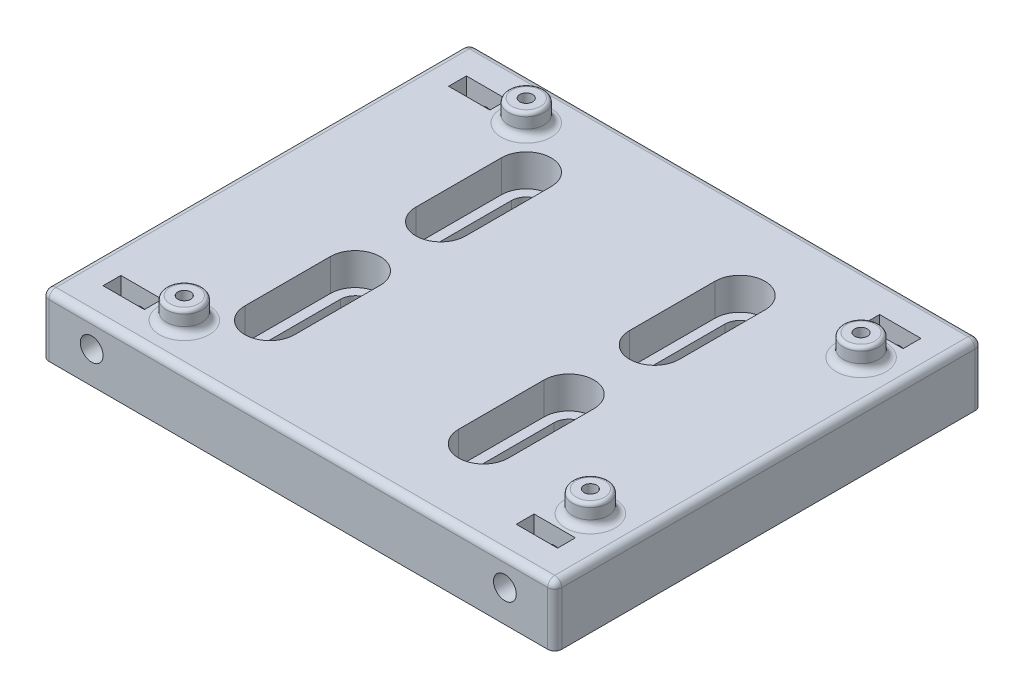
SolidWorks part; units mm, degrees
ref_plane "Front Plane" through (0, 0, 0) normal (0, 0, 1) x (1, 0, 0)
ref_plane "Top Plane" through (0, 0, 0) normal (0, 1, 0) x (1, 0, 0)
ref_plane "Right Plane" through (0, 0, 0) normal (1, 0, 0) x (0, 0, -1)
sketch "Sketch1" plane through (0, 0, 0) normal (0, 1, 0) x (1, 0, 0)
  line L0 (35, 0) -> (35, -56)
  line L1 (0, 0) -> (70, 0)
  line L2 (0, 0) -> (0, -56)
  line L3 (0, -56) -> (70, -56)
  line L4 (70, 0) -> (70, -56)
  line L5 (0, -28) -> (70, -28)
  line L6 (17.9, -10) -> (17.9, -22)
  line L7 (22.1, -22) -> (22.1, -10)
  line L8 (47.9, -22) -> (47.9, -10)
  line L9 (52.1, -10) -> (52.1, -22)
  line L10 (22.1, -34) -> (22.1, -46)
  line L11 (17.9, -46) -> (17.9, -34)
  line L12 (52.1, -46) -> (52.1, -34)
  line L13 (47.9, -34) -> (47.9, -46)
  circle A0 centre (20, -10) radius 2.1
  circle A1 centre (20, -22) radius 2.1
  circle A2 centre (50, -22) radius 2.1
  circle A3 centre (50, -10) radius 2.1
  circle A4 centre (20, -34) radius 2.1
  circle A5 centre (20, -46) radius 2.1
  circle A6 centre (50, -34) radius 2.1
  circle A7 centre (50, -46) radius 2.1
  dimension "D3" = 10
  dimension "D5" = 6
  dimension "D1" = 70
  dimension "D2" = 56
  dimension "D4" = 20
  dimension "D6" = 20
extrude "Boss-Extrude1" add sketch "Sketch1" along normal blind 4 contours L2 L5 L0 L1 A1 L6 A0 L7 | L0 L5 L4 L1 L8 A3 L9 A2 | L5 L0 L3 L4 A7 L13 A6 L12 | L5 L2 L3 L0 L10 A5 L11 A4 region at (52.6754, 0, 13.8597) region at (17.3246, 0, 13.8597) region at (52.6754, 0, 42.1403) region at (17.3246, 0, 42.1403)
sketch "Sketch2" plane through (0, 4, 0) normal (0, 1, 0) x (1, 0, 0)
  line L18 (23.5, -22) -> (23.5, -10)
  line L19 (16.5, -10) -> (16.5, -22)
  line L20 (23.5, -22) -> (23.5, -10)
  line L21 (16.5, -10) -> (16.5, -22)
  line L35 (46.5, -10) -> (46.5, -22)
  line L36 (53.5, -22) -> (53.5, -10)
  line L37 (46.5, -10) -> (46.5, -22)
  line L38 (53.5, -22) -> (53.5, -10)
  line L43 (16.5, -34) -> (16.5, -46)
  line L44 (23.5, -46) -> (23.5, -34)
  line L45 (16.5, -34) -> (16.5, -46)
  line L46 (23.5, -46) -> (23.5, -34)
  line L50 (0, 0) -> (70, 0)
  line L51 (46.5, -34) -> (46.5, -46)
  line L52 (53.5, -46) -> (53.5, -34)
  line L53 (46.5, -34) -> (46.5, -46)
  line L54 (53.5, -46) -> (53.5, -34)
  line L55 (0, 0) -> (0, -56)
  line L56 (0, -56) -> (70, -56)
  line L57 (70, 0) -> (70, -56)
  arc A8 (16.5, -22) -> (23.5, -22) centre (20, -22) ccw
  arc A9 (23.5, -10) -> (16.5, -10) centre (20, -10) ccw
  arc A10 (16.5, -22) -> (23.5, -22) centre (20, -22) ccw
  arc A11 (23.5, -10) -> (16.5, -10) centre (20, -10) ccw
  arc A30 (46.5, -22) -> (53.5, -22) centre (50, -22) ccw
  arc A31 (53.5, -10) -> (46.5, -10) centre (50, -10) ccw
  arc A32 (46.5, -22) -> (53.5, -22) centre (50, -22) ccw
  arc A33 (53.5, -10) -> (46.5, -10) centre (50, -10) ccw
  arc A40 (16.5, -46) -> (23.5, -46) centre (20, -46) ccw
  arc A41 (23.5, -34) -> (16.5, -34) centre (20, -34) ccw
  arc A42 (16.5, -46) -> (23.5, -46) centre (20, -46) ccw
  arc A43 (23.5, -34) -> (16.5, -34) centre (20, -34) ccw
  arc A50 (46.5, -46) -> (53.5, -46) centre (50, -46) ccw
  arc A51 (53.5, -34) -> (46.5, -34) centre (50, -34) ccw
  arc A52 (46.5, -46) -> (53.5, -46) centre (50, -46) ccw
  arc A53 (53.5, -34) -> (46.5, -34) centre (50, -34) ccw
  dimension "D2" = 1.4
  dimension "D1" = 1.4
  dimension "D3" = 1.4
  dimension "D4" = 1.4
extrude "Boss-Extrude2" add sketch "Sketch2" along normal blind 4.5
sketch "Sketch5" plane through (0, 0, 56) normal (0, 0, 1) x (1, 0, 0)
  line L1 (0, 8.5) -> (70, 8.5)
  line L2 (0, 8.5) -> (0, 0)
  line L3 (0, 0) -> (70, 0)
  line L4 (70, 8.5) -> (70, 0)
extrude "Boss-Extrude3" add sketch "Sketch5" along normal blind 2
sketch "Sketch6" plane through (0, 0, 0) normal (0, 0, -1) x (-1, 0, 0)
  line L1 (-70, 8.5) -> (0, 8.5)
  line L2 (-70, 8.5) -> (-70, 0)
  line L3 (-70, 0) -> (0, 0)
  line L4 (0, 8.5) -> (0, 0)
extrude "Boss-Extrude4" add sketch "Sketch6" along normal blind 2
sketch "Sketch7" plane through (0, 8.5, 0) normal (0, 1, 0) x (1, 0, 0)
  line L0 (0, 2) -> (0, -58) construction
  line L1 (0, -28) -> (70, -28)
  line L2 (70, -58) -> (70, 2) construction
  circle A0 centre (14, -4) radius 0.9
  circle A1 centre (14, -52) radius 0.9
  circle A2 centre (14, -4) radius 2.5
  circle A3 centre (14, -52) radius 2.5
  circle A4 centre (66, -47) radius 0.9
  circle A5 centre (66, -47) radius 2.5
  circle A6 centre (39.3723, -13.6748) radius 2.5
  dimension "D1" = 24
  dimension "D5" = 52
  dimension "D2" = 24
  dimension "D3" = 14
  dimension "D4" = 14
  dimension "D6" = 5
extrude "Boss-Extrude5" add sketch "Sketch7" along normal blind 3 contours A2 A0 | A3 A1 | A6 | A4 | A5 region at (11.5707, 8.5, 4) region at (11.5707, 8.5, 52) region at (66, 8.5, 47) region at (39.3723, 8.5, 13.6748)
fillet "Fillet2" radius 1 4 edges at (66, 8.5, 49.5) (39.3723, 8.5, 16.1748) (14, 8.5, 54.5) (14, 8.5, 6.5)
fillet "Fillet4" radius 0.5 4 edges at (66, 11.5, 49.5) (39.3723, 11.5, 16.1748) (14, 11.5, 54.5) (14, 11.5, 6.5)
extrude "Cut-Extrude6" cut sketch "Sketch7<4>" against normal blind 30 contours A1 | A4
sketch "Sketch7<4>" plane through (0, 8.5, 0) normal (0, 1, 0) x (1, 0, 0) same geometry as "Sketch7"
sketch "Sketch8" plane through (70, 0, 0) normal (1, 0, 0) x (0, 0, -1)
  line L1 (-58, 8.5) -> (2, 8.5)
  line L2 (-58, 8.5) -> (-58, 0)
  line L3 (-58, 0) -> (2, 0)
  line L4 (2, 8.5) -> (2, 0)
extrude "Boss-Extrude6" add sketch "Sketch8" along normal blind 2
sketch "Sketch9" plane through (0, 0, 58) normal (0, 0, 1) x (1, 0, 0)
  line L1 (7, 1.1514) -> (9.9, 2.8257)
  line L2 (9.9, 2.8257) -> (9.9, 6.1743)
  line L3 (9.9, 6.1743) -> (7, 7.8486)
  line L4 (7, 7.8486) -> (4.1, 6.1743)
  line L5 (4.1, 6.1743) -> (4.1, 2.8257)
  line L6 (4.1, 2.8257) -> (7, 1.1514)
  line L7 (72, 8.5) -> (0, 8.5) construction
  line L8 (0, 8.5) -> (0, 0) construction
  line L9 (4.1, 6.1743) -> (4.1, 8.5)
  line L10 (4.1, 8.5) -> (9.9, 8.5)
  line L11 (9.9, 8.5) -> (9.9, 6.1743)
  line L12 (36, 8.5) -> (36, 0)
  line L13 (0, 0) -> (72, 0) construction
  line L14 (62.1, 8.5) -> (62.1, 6.1743)
  line L15 (67.9, 8.5) -> (62.1, 8.5)
  line L16 (67.9, 6.1743) -> (67.9, 8.5)
  line L17 (67.9, 2.8257) -> (65, 1.1514)
  line L18 (67.9, 6.1743) -> (67.9, 2.8257)
  line L19 (65, 7.8486) -> (67.9, 6.1743)
  line L20 (62.1, 6.1743) -> (65, 7.8486)
  line L21 (62.1, 2.8257) -> (62.1, 6.1743)
  line L22 (65, 1.1514) -> (62.1, 2.8257)
  circle A0 centre (7, 4.5) radius 1.6
  circle A1 centre (7, 4.5) radius 2.9 construction
  circle A2 centre (65, 4.5) radius 2.9 construction
  circle A3 centre (65, 4.5) radius 1.6
  line M11 (72, 8.5) -> (0, 8.5)
  dimension "D1" = 4
  dimension "D2" = 5.8
  dimension "D3" = 7
extrude "Cut-Extrude2" cut sketch "Sketch9" against normal blind 7 contours L11 L9 L4 L3 M11 | L5 L6 L1 L2 L3 L4 A0 | A0 | L14 L20 L19 L16 M11 | L22 L17 L18 L19 L20 L21 A3 | A3 region at (5.5943, 2.0653, 58) region at (65, 8.4375, 58) region at (8.4812, 7.0656, 58) region at (63.5943, 6.9347, 58) region at (7, 4.5, 58) region at (65, 4.5, 58)
extrude "Boss-Extrude8" add sketch "Sketch9<8>" against normal blind 4.5 contours L5 L6 L1 L2 L3 L4 A0 | L11 L9 L4 L3 M11 | L14 L20 L19 L16 M11 | L22 L17 L18 L19 L20 L21 A3 region at (5.5943, 2.0653, 58) region at (65, 8.4375, 58) region at (8.4812, 7.0656, 58) region at (63.5943, 6.9347, 58)
sketch "Sketch9<8>" plane through (0, 0, 58) normal (0, 0, 1) x (1, 0, 0) same geometry as "Sketch9"
extrude "Cut-Extrude4" cut sketch "Sketch9<9>" against normal blind 10 contours A0 | A3 region at (7, 4.5, 58) region at (65, 4.5, 58)
sketch "Sketch9<9>" plane through (0, 0, 58) normal (0, 0, 1) x (1, 0, 0) same geometry as "Sketch9"
sketch "Sketch11" plane through (0, 0, -2) normal (0, 0, -1) x (-1, 0, 0)
  line L1 (-72, 0) -> (2.9129, 0)
  line L2 (-72, 0) -> (-72, 22.4588)
  line L3 (-72, 22.4588) -> (2.9129, 22.4588)
  line L4 (2.9129, 0) -> (2.9129, 22.4588)
extrude "Cut-Extrude5" cut sketch "Sketch11" against normal blind 30
mirror "Mirror2" about plane through (0, 0, 28) normal (0, 0, 1) of bodies 113
fillet "Fillet5" radius 1 8 edges at (72, 8.5, 28) (36, 8.5, 58) (0, 8.5, 28) (36, 8.5, -2) (0, 4.25, -2) (72, 4.25, -2) (72, 4.25, 58) (0, 4.25, 58)
